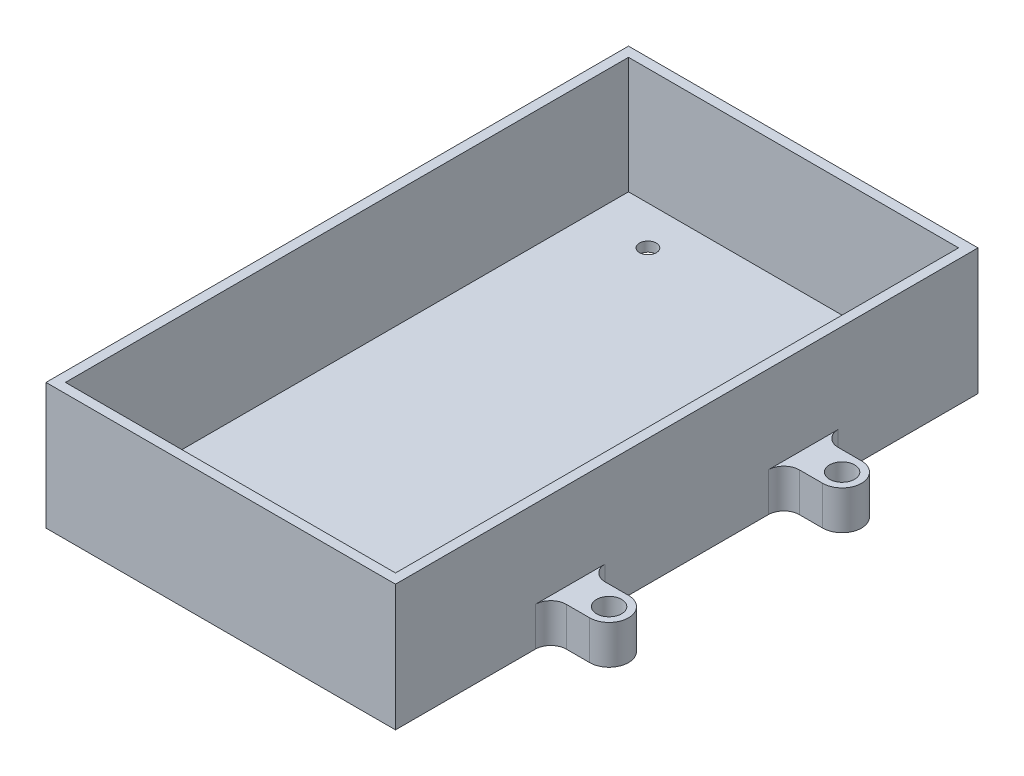
SolidWorks part; units mm, degrees
ref_plane "Front Plane" through (0, 0, 0) normal (0, 0, 1) x (1, 0, 0)
ref_plane "Top Plane" through (0, 0, 0) normal (0, 1, 0) x (1, 0, 0)
ref_plane "Right Plane" through (0, 0, 0) normal (1, 0, 0) x (0, 0, -1)
sketch "Sketch1" plane through (0, 0, 0) normal (0, 1, 0) x (1, 0, 0)
  line L0 (-17.4625, 39.6875) -> (17.4625, 39.6875) construction
  line L1 (26.9875, -46.0375) -> (-26.9875, -46.0375)
  line L2 (26.9875, -46.0375) -> (26.9875, 46.0375)
  line L3 (26.9875, 46.0375) -> (-26.9875, 46.0375)
  line L4 (-26.9875, -46.0375) -> (-26.9875, 46.0375)
  line L5 (26.9875, -46.0375) -> (-26.9875, 46.0375) construction
  line L6 (26.9875, 46.0375) -> (-26.9875, -46.0375) construction
  line L7 (0, 0) -> (26.9875, 0)
  line L8 (28.575, 47.625) -> (-28.575, 47.625)
  line L9 (28.575, 47.625) -> (28.575, -47.625)
  line L10 (28.575, -47.625) -> (-28.575, -47.625)
  line L11 (-28.575, 47.625) -> (-28.575, -47.625)
  line L12 (28.575, 47.625) -> (-28.575, -47.625) construction
  line L13 (28.575, -47.625) -> (-28.575, 47.625) construction
  line L14 (-17.4625, -39.6875) -> (17.4625, -39.6875) construction
  circle A0 centre (-17.4625, 39.6875) radius 1.375
  circle A1 centre (17.4625, 39.6875) radius 1.375
  circle A2 centre (-17.4625, -39.6875) radius 1.375
  circle A3 centre (17.4625, -39.6875) radius 1.375
  point P0 (0, 0)
  point P10 (0, 39.6875)
  point P12 (0, 0)
  point P22 (0, -39.6875)
  dimension "D5" = 2.75
  dimension "D1" = 53.975
  dimension "D2" = 92.075
  dimension "D3" = 34.925
  dimension "D4" = 6.35
  dimension "D6" = 1.5875
  dimension "D7" = 1.5875
extrude "Boss-Extrude1" add sketch "Sketch1" against normal blind 1.5875 contours L4 L1 L2 L3 A1 A0 | L8 L11 L10 L9 L1 L4 L3 L2 region at (0, 0, 44.9702) region at (27.4642, 0, 0)
extrude "Boss-Extrude2" add sketch "Sketch1<3>" along normal blind 19.05 contours L8 L11 L10 L9 L1 L4 L3 L2 region at (27.4642, 0, 0)
sketch "Sketch1<3>" plane through (0, 0, 0) normal (0, 1, 0) x (1, 0, 0) same geometry as "Sketch1"
sketch "Sketch3" plane through (0, -1.5875, 0) normal (0, -1, 0) x (1, 0, 0)
  line L0 (28.575, -47.625) -> (28.575, 47.625) construction
  line L1 (34.925, 22.225) -> (28.575, 22.225)
  line L2 (28.575, 22.225) -> (28.575, 15.875)
  line L3 (28.575, 15.875) -> (34.925, 15.875)
  line L4 (0, 0) -> (28.575, 0) construction
  line L5 (28.575, -15.875) -> (34.925, -15.875)
  line L6 (28.575, -22.225) -> (28.575, -15.875)
  line L7 (34.925, -22.225) -> (28.575, -22.225)
  circle A0 centre (34.925, 19.05) radius 2.05
  circle A1 centre (34.925, 19.05) radius 3.175
  circle A2 centre (34.925, -19.05) radius 3.175
  circle A3 centre (34.925, -19.05) radius 2.05
  line M8 (28.575, -47.625) -> (28.575, 47.625)
  dimension "D1" = 4.1
  dimension "D2" = 6.35
  dimension "D3" = 6.35
  dimension "D4" = 19.05
extrude "Boss-Extrude5" add sketch "Sketch3" against normal blind 6.35 contours A1 L1 L2 | A0 | A1 L3 M8 | L6 A2 L5 | A2 A3 | L7 A2 M8 | A1 region at (30.5683, -1.5875, 19.05) region at (30.5683, -1.5875, -19.05) region at (37.1066, -1.5875, -16.8684) region at (34.925, -1.5875, 19.05)
fillet "Fillet1" radius 2.54 4 edges at (28.575, 1.5875, -22.225) (28.575, 1.5875, -15.875) (28.575, 1.5875, 15.875) (28.575, 1.5875, 22.225)
